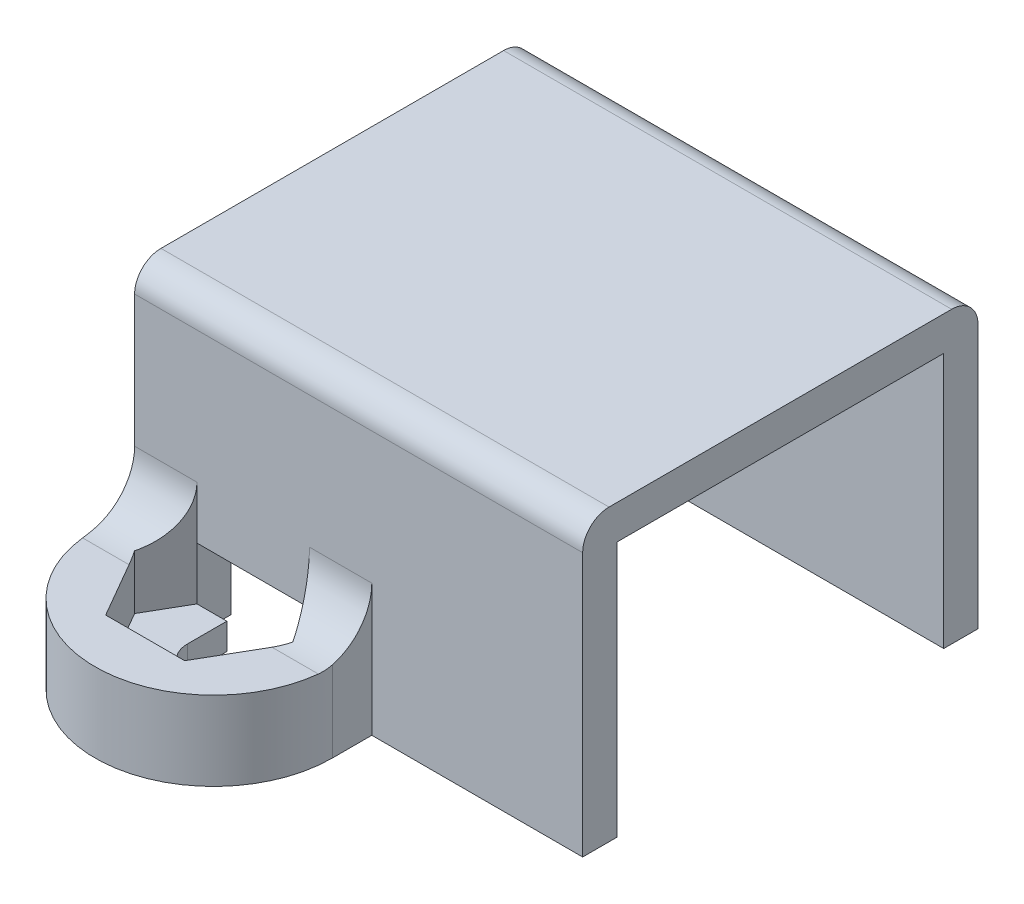
SolidWorks part; units mm, degrees
material "ABS"
ref_plane "Alzado" through (0, 0, 0) normal (0, 0, 1) x (1, 0, 0)
ref_plane "Planta" through (0, 0, 0) normal (0, 1, 0) x (1, 0, 0)
ref_plane "Vista lateral" through (0, 0, 0) normal (1, 0, 0) x (0, 0, -1)
sketch "Croquis1" plane through (0, 0, 0) normal (0, 1, 0) x (1, 0, 0)
  line L1 (-8.5, -13.5) -> (8.5, -13.5)
  line L2 (-8.5, -13.5) -> (-8.5, 13.5)
  line L3 (-8.5, 13.5) -> (8.5, 13.5)
  line L4 (8.5, -13.5) -> (8.5, 13.5)
  line L5 (-8.5, -13.5) -> (8.5, 13.5) construction
  line L6 (-8.5, 13.5) -> (8.5, -13.5) construction
  point P0 (0, 0)
  dimension "D1" = 17
  dimension "D2" = 27
extrude "Saliente-Extruir1" add sketch "Croquis1" along normal blind 11
sketch "Croquis2" plane through (0, 11, 0) normal (0, 1, 0) x (1, 0, 0)
  line L1 (-8.5, -7.5) -> (8.5, -7.5) construction
  line L2 (-8.5, 13.5) -> (-8.5, -13.5) construction
  line L3 (-8.5, 7.5) -> (8.5, 7.5) construction
  line L4 (-8.5, 13.5) -> (8.5, 13.5)
  line L5 (-8.5, 13.5) -> (-8.5, 7.5)
  line L6 (-8.5, 7.5) -> (8.5, 7.5)
  line L7 (8.5, 13.5) -> (8.5, 7.5)
  line L8 (-8.5, -7.5) -> (8.5, -7.5)
  line L9 (-8.5, -7.5) -> (-8.5, -13.5)
  line L10 (-8.5, -13.5) -> (8.5, -13.5)
  line L11 (8.5, -7.5) -> (8.5, -13.5)
  point P0 (0, 0)
  dimension "D1" = 6
  dimension "D2" = 6
extrude "Cortar-Extruir1" cut sketch "Croquis2" against normal blind 6
sketch "Croquis3" plane through (0, 0, 13.5) normal (0, 0, 1) x (1, 0, 0)
  line L0 (8.5, 5) -> (-8.5, 5) construction
  line L1 (8.5, 0) -> (0.5, 0)
  line L2 (8.5, 0) -> (8.5, 5)
  line L3 (8.5, 5) -> (0.5, 5)
  line L4 (0.5, 0) -> (0.5, 5)
  dimension "D1" = 8
extrude "Cortar-Extruir2" cut sketch "Croquis3" against normal blind 6
sketch "Croquis4" plane through (0, 0, -13.5) normal (0, 0, -1) x (-1, 0, 0)
  line L0 (8.5, 5) -> (-8.5, 5) construction
  line L1 (-8.5, 0) -> (-0.5, 0)
  line L2 (-8.5, 0) -> (-8.5, 5)
  line L3 (-8.5, 5) -> (-0.5, 5)
  line L4 (-0.5, 0) -> (-0.5, 5)
  dimension "D1" = 8
extrude "Cortar-Extruir3" cut sketch "Croquis4" against normal blind 6
sketch "Croquis5" plane through (0, 5, 0) normal (0, 1, 0) x (1, 0, 0)
  line L0 (-8.5, 9) -> (-8.5, 13.5)
  line L1 (0.5, 13.5) -> (-8.5, 13.5) construction
  line L2 (0.5, 7.5) -> (0.5, 13.5) construction
  line L3 (-8.5, 13.5) -> (-8.5, 7.5) construction
  line L4 (-8.5, 13.5) -> (0.5, 13.5)
  line L5 (0.5, 13.5) -> (0.5, 9)
  line L6 (-8.5, -9) -> (-8.5, -13.5)
  line L14 (-8.5, -13.5) -> (0.5, -13.5) construction
  line L15 (-8.5, -7.5) -> (-8.5, -13.5) construction
  line L16 (0.5, -7.5) -> (0.5, -13.5) construction
  line L17 (-8.5, -13.5) -> (0.5, -13.5)
  line L18 (0.5, -13.5) -> (0.5, -9)
  line L19 (0.5, -7.5) -> (-8.5, -7.5) construction
  arc A0 (-4, 13.5) -> (0.5, 9) centre (-4, 9) cw
  arc A1 (-8.5, 9) -> (-4, 13.5) centre (-4, 9) cw
  arc A2 (-4, -13.5) -> (-8.5, -9) centre (-4, -9) cw
  arc A3 (-4, -13.5) -> (0.5, -9) centre (-4, -9) ccw
  line M1 (0.5, 7.5) -> (0.5, 13.5)
  line M2 (0.5, 13.5) -> (-8.5, 13.5)
  line M3 (-8.5, 13.5) -> (-8.5, 7.5)
  dimension "D1" = 4.5
  dimension "D2" = 1.5
extrude "Cortar-Extruir8" cut sketch "Croquis5" against normal blind 6 contours A1 L4 M3 | A0 M2 M1 | L17 A2 L6 | A3 L17 L18
sketch "Croquis7" plane through (0, 5, 0) normal (0, 1, 0) x (1, 0, 0)
  line L0 (-8.5, 7.5) -> (-8.5, 9)
  line L1 (-8.5, 7.5) -> (0.5, 7.5)
  line L2 (-8.5, 7.5) -> (8.5, 7.5) construction
  line L3 (-8.5, 7.5) -> (0.5, 7.5) construction
  line L4 (0.5, 7.5) -> (0.5, 9)
  line L5 (-8.5, -9) -> (-8.5, -7.5)
  line L7 (-8.5, -7.5) -> (0.5, -7.5)
  line L8 (0.5, -7.5) -> (0.5, -9)
  arc A0 (0.5, 9) -> (-8.5, 9) centre (-4, 9) ccw
  arc A1 (-8.5, -9) -> (0.5, -9) centre (-4, -9) ccw
  arc A2 (-8.5, -9) -> (0.5, -9) centre (-4, -9) ccw construction
  dimension "D1" = 4.5
extrude "Cortar-Extruir16" cut sketch "Croquis7" against normal blind 2
sketch "Croquis10" plane through (0, 3, 0) normal (0, 1, 0) x (1, 0, 0)
  line L0 (-6.134, 7.5) -> (-1.866, 7.5)
  line L1 (-8.5, 7.5) -> (0.5, 7.5) construction
  line L3 (-1, 9) -> (-2.5, 11.5981)
  line L4 (-2.5, 11.5981) -> (-5.5, 11.5981)
  line L5 (-5.5, 11.5981) -> (-7, 9)
  line L6 (-7, 9) -> (-6.134, 7.5)
  line L8 (-1.866, 7.5) -> (-1, 9)
  line L9 (-4, 6.4019) -> (-2.5, 6.4019)
  arc A1 (-1.8787, 7.5) -> (-1.75, 7.701) centre (-4, 9) ccw construction
  arc A2 (-6.25, 7.701) -> (-6.1213, 7.5) centre (-4, 9) ccw construction
  dimension "D1" = 3
  dimension "D2" = 1.5
extrude "Cortar-Extruir17" cut sketch "Croquis10" against normal blind 2
sketch "Croquis11" plane through (0, 3, 0) normal (0, 1, 0) x (1, 0, 0)
  line L1 (0.5, -7.5) -> (-8.5, -7.5) construction
  line L2 (-6.134, -7.5) -> (-1.866, -7.5)
  line L3 (-1, -9) -> (-1.866, -7.5)
  line L5 (-6.134, -7.5) -> (-7, -9)
  line L6 (-7, -9) -> (-5.5, -11.5981)
  line L7 (-5.5, -11.5981) -> (-2.5, -11.5981)
  line L8 (-2.5, -11.5981) -> (-1, -9)
  line L9 (8.5, -7.5) -> (-8.5, -7.5) construction
  line L11 (-2.5, -6.4019) -> (-4, -6.4019)
  arc A0 (-1.75, -7.701) -> (-1.8787, -7.5) centre (-4, -9) ccw construction
  arc A1 (-6.1213, -7.5) -> (-6.25, -7.701) centre (-4, -9) ccw construction
extrude "Cortar-Extruir18" cut sketch "Croquis11" against normal blind 2
fillet "Redondeo5" radius 2 4 edges at (-0.683, 3, 7.5) (-7.317, 3, 7.5) (-0.683, 3, -7.5) (-7.317, 3, -7.5)
sketch "Croquis12" plane through (-8.5, 0, 0) normal (-1, 0, 0) x (0, 0, 1)
  line L0 (-6.2, 0) -> (6.2, 0)
  line L1 (-9, 0) -> (9, 0) construction
  line L5 (-6.2, 0) -> (-6.2, 7.7)
  line L7 (6.2, 0) -> (6.2, 7.7)
  line L10 (-4.2, 9.7) -> (4.2, 9.7)
  arc A0 (-4.2, 9.7) -> (-6.2, 7.7) centre (-4.2, 7.7) ccw
  arc A1 (6.2, 7.7) -> (4.2, 9.7) centre (4.2, 7.7) ccw
  dimension "D1" = 2
  dimension "D2" = 8.4
extrude "Cortar-Extruir19" cut sketch "Croquis12" against normal blind 17
sketch "Croquis13" plane through (8.5, 0, 0) normal (1, 0, 0) x (0, 0, -1)
  line L0 (-6.2, 7.7) -> (-6.2, 9.7)
  line L1 (-6.2, 9.7) -> (-4.2, 9.7)
  line L2 (6.2, 7.7) -> (6.2, 9.7)
  line L3 (6.2, 9.7) -> (4.2, 9.7)
  arc A0 (-4.2, 9.7) -> (-6.2, 7.7) centre (-4.2, 7.7) ccw
  arc A1 (6.2, 7.7) -> (4.2, 9.7) centre (4.2, 7.7) ccw construction
  arc A2 (6.2, 7.7) -> (4.2, 9.7) centre (4.2, 7.7) ccw
extrude "Cortar-Extruir20" cut sketch "Croquis13" against normal blind 10
fillet "Redondeo6" radius 1 2 edges at (0, 11, -7.5) (0, 11, 7.5)
sketch "Croquis14" plane through (0, 1, 0) normal (0, 1, 0) x (1, 0, 0)
  line L0 (-5, 9) -> (-5, 7.5)
  line L1 (-8.5, 7.5) -> (8.5, 7.5) construction
  line L2 (-3, 9) -> (-3, 7.5)
  line L3 (-6.134, 7.5) -> (-1.866, 7.5) construction
  line L4 (-3, 7.5) -> (-5, 7.5)
  arc A1 (-3, 9) -> (-5, 9) centre (-4, 9) ccw
extrude "Cortar-Extruir21" cut sketch "Croquis14" against normal blind 1 contours A1 L0 L4 L2
sketch "Croquis15" plane through (0, 1, 0) normal (0, 1, 0) x (1, 0, 0)
  line L0 (-5, -9) -> (-5, -7.5)
  line L1 (-1.866, -7.5) -> (-6.134, -7.5) construction
  line L2 (-5, -7.5) -> (-3, -7.5)
  line L3 (-3, -7.5) -> (-3, -9)
  arc A1 (-5, -9) -> (-3, -9) centre (-4, -9) ccw
extrude "Cortar-Extruir22" cut sketch "Croquis15" against normal blind 1
sketch "Croquis16" plane through (0, 0, -7.5) normal (0, 0, -1) x (-1, 0, 0)
  line L0 (1.866, 3) -> (6.134, 3)
  line L1 (1.866, 1) -> (1.866, 5) construction
  line L2 (6.134, 1) -> (6.134, 5) construction
  line L3 (6.134, 3) -> (6.134, 1)
  line L4 (6.134, 1) -> (5, 1)
  line L7 (3, 1) -> (1.866, 1)
  line L8 (1.866, 1) -> (1.866, 3)
  line L9 (3, 1) -> (5, 1)
extrude "Cortar-Extruir26" cut sketch "Croquis16" against normal blind 1.3 contours L0 L3 L4 L9 L7 L8
sketch "Croquis17" plane through (0, 0, 7.5) normal (0, 0, 1) x (1, 0, 0)
  line L0 (-6.134, 3) -> (-1.866, 3)
  line L1 (-6.134, 1) -> (-6.134, 5) construction
  line L2 (-1.866, 1) -> (-1.866, 5) construction
  line L3 (-1.866, 3) -> (-1.866, 1)
  line L4 (-1.866, 1) -> (-6.134, 1)
  line L5 (-6.134, 1) -> (-6.134, 3)
extrude "Cortar-Extruir27" cut sketch "Croquis17" against normal blind 1.3
sketch "Croquis19" plane through (0, 0, 6.2) normal (0, 0, -1) x (-1, 0, 0)
  line L0 (1.866, 1) -> (1.866, 0)
  line L1 (-8.5, 0) -> (8.5, 0) construction
  line L2 (1.866, 0) -> (6.134, 0)
  line L3 (6.134, 0) -> (6.134, 1)
  line L4 (6.134, 1) -> (1.866, 1)
extrude "Cortar-Extruir28" cut sketch "Croquis19" against normal blind 1.3
sketch "Croquis20" plane through (0, 0, -6.2) normal (0, 0, 1) x (1, 0, 0)
  line L0 (-6.134, 1) -> (-1.866, 1)
  line L1 (-1.866, 1) -> (-1.866, 0)
  line L2 (8.5, 0) -> (-8.5, 0) construction
  line L3 (-1.866, 0) -> (-6.134, 0)
  line L4 (-6.134, 0) -> (-6.134, 1)
extrude "Cortar-Extruir29" cut sketch "Croquis20" against normal blind 1.3
